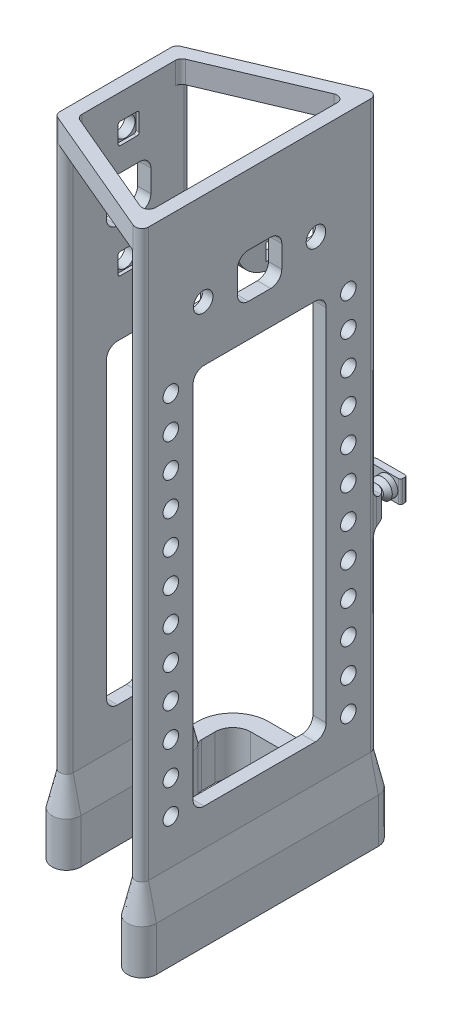
SolidWorks part; units mm, degrees
ref_plane "Front Plane" through (0, 0, 0) normal (0, 0, 1) x (1, 0, 0)
ref_plane "Top Plane" through (0, 0, 0) normal (0, 1, 0) x (1, 0, 0)
ref_plane "Right Plane" through (0, 0, 0) normal (1, 0, 0) x (0, 0, -1)
sketch "Sketch3" plane through (0, 0, 0) normal (0, 1, 0) x (1, 0, 0)
  line L0 (0, 83.3807) -> (0, -77.8886) construction
  line L1 (-38.4941, 0) -> (38.1013, 0) construction
  line L2 (-14.75, 446.5322) -> (-14.75, -531.1458) construction
  line L3 (-16.75, 12.5) -> (-16.75, -12.5)
  line L4 (-12.75, 12.5) -> (-12.75, -12.5)
  line L5 (-11.5, 12.5) -> (-11.5, -12.5)
  line L6 (-18, 12.5) -> (-18, -12.5)
  line L7 (11.5, 25) -> (11.5, -25)
  line L8 (12.75, 25) -> (12.75, -25)
  line L9 (16.75, 25) -> (16.75, -25)
  line L10 (18, 25) -> (18, -25)
  arc A0 (-16.75, 12.5) -> (-12.75, 12.5) centre (-14.75, 12.5) cw
  arc A1 (-16.75, -12.5) -> (-12.75, -12.5) centre (-14.75, -12.5) ccw
  arc A2 (-18, -12.5) -> (-11.5, -12.5) centre (-14.75, -12.5) ccw
  arc A3 (-18, 12.5) -> (-11.5, 12.5) centre (-14.75, 12.5) cw
  arc A4 (18, -25) -> (11.5, -25) centre (14.75, -25) cw
  arc A5 (16.75, -25) -> (12.75, -25) centre (14.75, -25) cw
  arc A6 (16.75, 25) -> (12.75, 25) centre (14.75, 25) ccw
  arc A7 (18, 25) -> (11.5, 25) centre (14.75, 25) ccw
  point P10 (-12.75, 0)
  point P15 (-16.75, 0)
  dimension "D3" = 1.25
  dimension "D1" = 2
  dimension "D2" = 25
  dimension "D5" = 14.75
  dimension "D4" = 50
  dimension "D6" = 1.25
extrude "LowerColumnAttachment" add sketch "Sketch3" along normal blind 7.5
sketch "Sketch4" plane through (0, 7.5, 0) normal (0, 1, 0) x (1, 0, 0)
  line L0 (-11.5, -12.5) -> (-11.5, 12.5) construction
  line L1 (-18, 12.5) -> (-18, -12.5) construction
  line L2 (18, -25) -> (18, 25) construction
  line L3 (11.5, 25) -> (11.5, -25) construction
  line L4 (-11.5, -12.5) -> (-11.5, 12.5)
  line L5 (-18, 12.5) -> (-18, -12.5)
  line L6 (18, -25) -> (18, 25)
  line L7 (11.5, 25) -> (11.5, -25)
  arc A0 (-18, -12.5) -> (-11.5, -12.5) centre (-14.75, -12.5) ccw construction
  arc A1 (-11.5, 12.5) -> (-18, 12.5) centre (-14.75, 12.5) ccw construction
  arc A2 (18, 25) -> (11.5, 25) centre (14.75, 25) ccw construction
  arc A3 (11.5, -25) -> (18, -25) centre (14.75, -25) ccw construction
  arc A4 (-18, -12.5) -> (-11.5, -12.5) centre (-14.75, -12.5) ccw
  arc A5 (-11.5, 12.5) -> (-18, 12.5) centre (-14.75, 12.5) ccw
  arc A6 (18, 25) -> (11.5, 25) centre (14.75, 25) ccw
  arc A7 (11.5, -25) -> (18, -25) centre (14.75, -25) ccw
extrude "LowerColumnAttachmentCover" add sketch "Sketch4" along normal blind 2.5
sketch "Sketch5" plane through (0, 10, 0) normal (0, 1, 0) x (1, 0, 0)
  line L2 (-18, 12.5) -> (-18, -12.5) construction
  line L3 (-11.5, -12.5) -> (-11.5, 12.5) construction
  line L56 (-11.5, -12.5) -> (-11.5, 12.5) construction
  line L57 (-18, 12.5) -> (-18, -12.5) construction
  line L58 (-16.25, 12.5) -> (-16.25, -12.5)
  line L59 (-13.25, -12.5) -> (-13.25, 12.5)
  line L60 (18, -25) -> (18, 25) construction
  line L61 (11.5, 25) -> (11.5, -25) construction
  line L62 (18, -25) -> (18, 25) construction
  line L63 (11.5, 25) -> (11.5, -25) construction
  line L64 (16.25, -25) -> (16.25, 25)
  line L65 (13.25, 25) -> (13.25, -25)
  arc A2 (-18, -12.5) -> (-11.5, -12.5) centre (-14.75, -12.5) ccw construction
  arc A3 (-11.5, 12.5) -> (-18, 12.5) centre (-14.75, 12.5) ccw construction
  arc A56 (-11.5, 12.5) -> (-18, 12.5) centre (-14.75, 12.5) ccw construction
  arc A57 (-18, -12.5) -> (-11.5, -12.5) centre (-14.75, -12.5) ccw construction
  arc A58 (-13.25, 12.5) -> (-16.25, 12.5) centre (-14.75, 12.5) ccw
  arc A59 (-16.25, -12.5) -> (-13.25, -12.5) centre (-14.75, -12.5) ccw
  arc A60 (18, 25) -> (11.5, 25) centre (14.75, 25) ccw construction
  arc A61 (11.5, -25) -> (18, -25) centre (14.75, -25) ccw construction
  arc A62 (18, 25) -> (11.5, 25) centre (14.75, 25) ccw construction
  arc A63 (11.5, -25) -> (18, -25) centre (14.75, -25) ccw construction
  arc A64 (16.25, 25) -> (13.25, 25) centre (14.75, 25) ccw
  arc A65 (13.25, -25) -> (16.25, -25) centre (14.75, -25) ccw
  dimension "D1" = 1.75
  dimension "D2" = 1.75
extrude "UpperColumnExtrude" add sketch "Sketch5" along normal blind 130
sketch "Sketch6" plane through (16.25, 0, 0) normal (1, 0, 0) x (0, 0, -1)
  line L0 (0, 199.0142) -> (0, -58.1482) construction
  line L1 (20, 27.5) -> (20, 35) construction
  line L2 (-15, 28.25) -> (-15, 109.25)
  line L3 (-12.5, 111.75) -> (12.5, 111.75)
  line L4 (15, 28.25) -> (15, 109.25)
  line L5 (-12.5, 25.75) -> (12.5, 25.75)
  line L7 (-466.9223, 0) -> (90.0452, 0) construction
  line L8 (-25, 140) -> (-25, 10) construction
  line L9 (-25, 10) -> (25, 10) construction
  arc A0 (-15, 109.25) -> (-12.5, 111.75) centre (-12.5, 109.25) cw
  arc A1 (15, 109.25) -> (12.5, 111.75) centre (12.5, 109.25) ccw
  arc A2 (-15, 28.25) -> (-12.5, 25.75) centre (-12.5, 28.25) ccw
  arc A3 (15, 28.25) -> (12.5, 25.75) centre (12.5, 28.25) cw
  circle A4 centre (-20, 27.5) radius 1.75
  circle A5 centre (20, 27.5) radius 1.75
  circle A6 centre (20, 35) radius 1.75
  circle A7 centre (-20, 35) radius 1.75
  circle A8 centre (20, 42.5) radius 1.75
  circle A9 centre (-20, 42.5) radius 1.75
  circle A10 centre (20, 50) radius 1.75
  circle A11 centre (-20, 50) radius 1.75
  circle A12 centre (20, 57.5) radius 1.75
  circle A13 centre (-20, 57.5) radius 1.75
  circle A14 centre (20, 65) radius 1.75
  circle A15 centre (-20, 65) radius 1.75
  circle A16 centre (20, 72.5) radius 1.75
  circle A17 centre (-20, 72.5) radius 1.75
  circle A18 centre (20, 80) radius 1.75
  circle A19 centre (-20, 80) radius 1.75
  circle A20 centre (20, 87.5) radius 1.75
  circle A21 centre (-20, 87.5) radius 1.75
  circle A22 centre (20, 95) radius 1.75
  circle A23 centre (-20, 95) radius 1.75
  circle A24 centre (20, 102.5) radius 1.75
  circle A25 centre (-20, 102.5) radius 1.75
  circle A26 centre (20, 110) radius 1.75
  circle A27 centre (-20, 110) radius 1.75
  dimension "D3" = 2.5
  dimension "D7" = 3.5
  dimension "D2" = 2.5
  dimension "D4" = 2.5
  dimension "D10" = 2.5
  dimension "D1" = 30
  dimension "D5" = 5
  dimension "D6" = 17.5
  dimension "D9" = 7.5
  dimension "D8" = 12
extrude "HolesCut" cut sketch "Sketch6" against normal up to next (3 mm away)
sketch "Sketch7" plane through (0, 140, 0) normal (0, 1, 0) x (1, 0, 0)
  line L0 (14.1648, 26.3811) -> (-15.3352, 13.8811)
  line L1 (16.25, -25) -> (16.25, 25) construction
  line L2 (-16.25, 12.5) -> (-16.25, -12.5) construction
  line L3 (16.25, -25) -> (16.25, 25)
  line L4 (-16.25, 12.5) -> (-16.25, -12.5)
  line L5 (14.1648, -26.3811) -> (-15.3352, -13.8811)
  arc A0 (16.25, -25) -> (14.1648, -26.3811) centre (14.75, -25) cw
  arc A1 (-16.25, -12.5) -> (-15.3352, -13.8811) centre (-14.75, -12.5) ccw
  arc A2 (16.25, 25) -> (14.1648, 26.3811) centre (14.75, 25) ccw
  arc A3 (-16.25, 12.5) -> (-15.3352, 13.8811) centre (-14.75, 12.5) cw
  arc A4 (13.25, -25) -> (16.25, -25) centre (14.75, -25) ccw construction
  arc A5 (-16.25, -12.5) -> (-13.25, -12.5) centre (-14.75, -12.5) ccw construction
  arc A6 (-13.25, 12.5) -> (-16.25, 12.5) centre (-14.75, 12.5) ccw construction
  arc A7 (16.25, 25) -> (13.25, 25) centre (14.75, 25) ccw construction
extrude "TopSectionExtrude" add sketch "Sketch7" along normal blind 5
sketch "Sketch11" plane through (0, 145, 0) normal (0, 1, 0) x (1, 0, 0)
  line L4 (-13.25, -10.513) -> (-13.25, 10.513)
  line L5 (-12.3352, 11.8941) -> (11.1648, 21.8517)
  line L6 (-15.3352, -13.8811) -> (14.1648, -26.3811) construction
  line L7 (14.1648, 26.3811) -> (-15.3352, 13.8811) construction
  line L8 (13.25, -20.4706) -> (13.25, 20.4706)
  line L9 (-12.3352, -11.8941) -> (11.1648, -21.8517)
  line L10 (16.25, -25) -> (16.25, 25) construction
  line L11 (-16.25, 12.5) -> (-16.25, -12.5) construction
  arc A1 (-13.25, 10.513) -> (-12.3352, 11.8941) centre (-11.75, 10.513) cw
  arc A2 (13.25, 20.4706) -> (11.1648, 21.8517) centre (11.75, 20.4706) ccw
  arc A3 (-13.25, -10.513) -> (-12.3352, -11.8941) centre (-11.75, -10.513) ccw
  arc A4 (13.25, -20.4706) -> (11.1648, -21.8517) centre (11.75, -20.4706) cw
  dimension "D1" = 3
  dimension "D5" = 1.5
  dimension "D6" = 1.5
  dimension "D7" = 1.5
  dimension "D8" = 1.5
  dimension "D2" = 3
  dimension "D3" = 3
  dimension "D4" = 3
extrude "TopSectionCut" cut sketch "Sketch11" against normal up to next
chamfer "CounterWeightPassChamfer" distance 1.75 distance2 7.5 8 edges at (-16.25, 10, 0) (-14.75, 10, 14) (-14.75, 10, -14) (-13.25, 10, 0) (16.25, 10, 0) (14.75, 10, -26.5) (14.75, 10, 26.5) (13.25, 10, 0)
sketch "Sketch8" plane through (16.25, 0, 0) normal (1, 0, 0) x (0, 0, -1)
  line L1 (13.4332, 124.25) -> (-60.6379, 124.25) construction
  line L2 (0, 154.8726) -> (0, -73.7622) construction
  line L3 (-25, 145) -> (25, 145) construction
  circle A0 centre (12.7, 124.25) radius 2.2
  circle A1 centre (-12.7, 124.25) radius 2.2
  dimension "D1" = 4.4
  dimension "D2" = 12.7
  dimension "D5" = 4.4
  dimension "D3" = 12.7
  dimension "D4" = 20.75
extrude "SupportBearingWideHoles" cut sketch "Sketch8" against normal up to next
sketch "Sketch9" plane through (13.25, 0, 0) normal (-1, 0, 0) x (0, 0, 1)
  line L0 (0, 153.5325) -> (0, -8.1993) construction
  line L1 (12.7, 126.45) -> (12.7, 122.05) construction
  line L2 (14.9, 124.25) -> (10.5, 124.25) construction
  line L3 (10.325, 126.125) -> (10.325, 122.375)
  line L4 (10.825, 126.625) -> (14.575, 126.625)
  line L5 (10.825, 121.875) -> (14.575, 121.875)
  line L6 (15.075, 126.125) -> (15.075, 122.375)
  line L7 (-15.075, 126.125) -> (-15.075, 122.375)
  line L8 (-10.825, 121.875) -> (-14.575, 121.875)
  line L9 (-10.325, 126.125) -> (-10.325, 122.375)
  line L10 (-10.825, 126.625) -> (-14.575, 126.625)
  arc A2 (10.325, 126.125) -> (10.825, 126.625) centre (10.825, 126.125) cw
  arc A3 (10.325, 122.375) -> (10.825, 121.875) centre (10.825, 122.375) ccw
  arc A4 (15.075, 122.375) -> (14.575, 121.875) centre (14.575, 122.375) cw
  arc A5 (15.075, 126.125) -> (14.575, 126.625) centre (14.575, 126.125) ccw
  circle A7 centre (12.7, 124.25) radius 2.2 construction
  arc A8 (-15.075, 126.125) -> (-14.575, 126.625) centre (-14.575, 126.125) cw
  arc A9 (-15.075, 122.375) -> (-14.575, 121.875) centre (-14.575, 122.375) ccw
  arc A10 (-10.325, 122.375) -> (-10.825, 121.875) centre (-10.825, 122.375) cw
  arc A11 (-10.325, 126.125) -> (-10.825, 126.625) centre (-10.825, 126.125) ccw
  dimension "D3" = 0.5
  dimension "D1" = 4.75
  dimension "D2" = 4.75
extrude "SupportBearingWideCutOut" cut sketch "Sketch9" against normal blind 0.75
sketch "Sketch12" plane through (-13.25, 0, 0) normal (1, 0, 0) x (0, 0, -1)
  line L0 (0, 142.2043) -> (0, -19.6949) construction
  line L1 (-30.5042, 124.25) -> (31.5208, 124.25) construction
  line L2 (-25, 145) -> (25, 145) construction
  circle A0 centre (0, 136.95) radius 2.2
  circle A1 centre (0, 111.55) radius 2.2
  dimension "D1" = 4.4
  dimension "D2" = 4.4
  dimension "D3" = 20.75
  dimension "D4" = 12.7
  dimension "D5" = 12.7
extrude "SupportBearingNarrowHoles" cut sketch "Sketch12" against normal up to next
sketch "Sketch13" plane through (-13.25, 0, 0) normal (1, 0, 0) x (0, 0, -1)
  line L0 (2.2, 136.95) -> (-2.2, 136.95) construction
  line L1 (0, 139.15) -> (0, 134.75) construction
  line L2 (2.375, 135.075) -> (2.375, 138.825)
  line L3 (-1.875, 139.325) -> (1.875, 139.325)
  line L4 (-2.375, 135.075) -> (-2.375, 138.825)
  line L5 (-1.875, 134.575) -> (1.875, 134.575)
  line L6 (-12.7, 124.25) -> (12.7, 124.25) construction
  line L7 (-2.375, 113.425) -> (-2.375, 109.675)
  line L8 (-1.875, 109.175) -> (1.875, 109.175)
  line L9 (2.375, 113.425) -> (2.375, 109.675)
  line L10 (-1.875, 113.925) -> (1.875, 113.925)
  circle A0 centre (0, 136.95) radius 2.2 construction
  arc A1 (2.375, 138.825) -> (1.875, 139.325) centre (1.875, 138.825) ccw
  arc A2 (-2.375, 138.825) -> (-1.875, 139.325) centre (-1.875, 138.825) cw
  arc A3 (2.375, 135.075) -> (1.875, 134.575) centre (1.875, 135.075) cw
  arc A4 (-2.375, 135.075) -> (-1.875, 134.575) centre (-1.875, 135.075) ccw
  arc A5 (-2.375, 113.425) -> (-1.875, 113.925) centre (-1.875, 113.425) cw
  arc A6 (-2.375, 109.675) -> (-1.875, 109.175) centre (-1.875, 109.675) ccw
  arc A7 (2.375, 109.675) -> (1.875, 109.175) centre (1.875, 109.675) cw
  arc A8 (2.375, 113.425) -> (1.875, 113.925) centre (1.875, 113.425) ccw
  point P7 (-2.375, 136.95)
  point P16 (0, 139.325)
  point P22 (2.375, 136.95)
  dimension "D1" = 0.5
  dimension "D2" = 4.75
  dimension "D3" = 4.75
extrude "SupportBearingNarrowCutOut" cut sketch "Sketch13" against normal blind 0.75
sketch "Sketch14" plane through (-16.25, 0, 0) normal (-1, 0, 0) x (0, 0, 1)
  line L0 (0, 149.8595) -> (0, -14.9405) construction
  line L1 (-5, 94.25) -> (-5, 28.25)
  line L2 (-2.5, 96.75) -> (2.5, 96.75)
  line L3 (-2.5, 25.75) -> (2.5, 25.75)
  line L4 (5, 94.25) -> (5, 28.25)
  line L5 (-8.5712, 124.25) -> (7.7144, 124.25) construction
  line L6 (-5, 121.75) -> (-5, 126.75)
  line L7 (-2.5, 129.25) -> (2.5, 129.25)
  line L8 (5, 121.75) -> (5, 126.75)
  line L9 (-2.5, 119.25) -> (2.5, 119.25)
  arc A0 (-5, 94.25) -> (-2.5, 96.75) centre (-2.5, 94.25) cw
  arc A1 (-5, 28.25) -> (-2.5, 25.75) centre (-2.5, 28.25) ccw
  arc A2 (5, 28.25) -> (2.5, 25.75) centre (2.5, 28.25) cw
  arc A3 (5, 94.25) -> (2.5, 96.75) centre (2.5, 94.25) ccw
  circle A4 centre (20, 27.5) radius 1.75 construction
  circle A6 centre (0, 111.55) radius 2.2 construction
  circle A7 centre (0, 136.95) radius 2.2 construction
  arc A8 (-5, 126.75) -> (-2.5, 129.25) centre (-2.5, 126.75) cw
  arc A9 (5, 126.75) -> (2.5, 129.25) centre (2.5, 126.75) ccw
  arc A10 (-5, 121.75) -> (-2.5, 119.25) centre (-2.5, 121.75) ccw
  arc A11 (5, 121.75) -> (2.5, 119.25) centre (2.5, 121.75) cw
  circle A14 centre (20, 95) radius 1.75 construction
  dimension "D2" = 2.5
  dimension "D3" = 2.5
  dimension "D1" = 10
  dimension "D4" = 10
  dimension "D5" = 10
extrude "SupportBearingNarrowCentreCutOut" cut sketch "Sketch14" against normal up to next
sketch "Sketch15" plane through (16.25, 0, 0) normal (1, 0, 0) x (0, 0, -1)
  line L0 (2.5, 129.25) -> (-2.5, 129.25) construction
  line L1 (5, 121.75) -> (5, 126.75) construction
  line L2 (-2.5, 119.25) -> (2.5, 119.25) construction
  line L3 (-5, 126.75) -> (-5, 121.75) construction
  line L4 (2.5, 129.25) -> (-2.5, 129.25)
  line L5 (5, 121.75) -> (5, 126.75)
  line L6 (-2.5, 119.25) -> (2.5, 119.25)
  line L7 (-5, 126.75) -> (-5, 121.75)
  arc A0 (5, 126.75) -> (2.5, 129.25) centre (2.5, 126.75) ccw construction
  arc A1 (2.5, 119.25) -> (5, 121.75) centre (2.5, 121.75) ccw construction
  arc A2 (-5, 121.75) -> (-2.5, 119.25) centre (-2.5, 121.75) ccw construction
  arc A3 (-2.5, 129.25) -> (-5, 126.75) centre (-2.5, 126.75) ccw construction
  arc A4 (5, 126.75) -> (2.5, 129.25) centre (2.5, 126.75) ccw
  arc A5 (2.5, 119.25) -> (5, 121.75) centre (2.5, 121.75) ccw
  arc A6 (-5, 121.75) -> (-2.5, 119.25) centre (-2.5, 121.75) ccw
  arc A7 (-2.5, 129.25) -> (-5, 126.75) centre (-2.5, 126.75) ccw
extrude "SupportBearingWideCentreCutOut" cut sketch "Sketch15" against normal up to next
ref_plane "LimitSwitchSupportPlane" through (0, 105, 0) normal (0, 1, 0) x (1, 0, 0)
sketch "Sketch16" plane through (0, 105, 0) normal (0, 1, 0) x (1, 0, 0)
  line L0 (-15.5, 15) -> (-15.5, 12.5)
  line L1 (-15.5, 12.5) -> (-14, 12.5)
  line L2 (-14, 12.5) -> (-14, 15)
  line L3 (-13.7, 15.7141) -> (-11.25, 18.1156)
  line L4 (-14.75, -19.9286) -> (-14.75, 49.3932) construction
  line L5 (-11.5, -12.5) -> (-11.5, 12.5) construction
  line L6 (-18, 12.5) -> (-18, -12.5) construction
  line L7 (-16.25, 12.5) -> (-18, 12.5) construction
  line L8 (-10.5, 19.901) -> (-10.5, 30)
  line L9 (-10.5, 30) -> (-12, 30)
  line L10 (-12, 30) -> (-12, 19.901)
  line L11 (-14.75, 16.7854) -> (-12.3, 19.1868)
  line L12 (-11.25, 31.213) -> (-11.25, 17.258) construction
  arc A0 (-15.5, 15) -> (-14.75, 16.7854) centre (-13, 15) cw
  arc A1 (-14, 15) -> (-13.7, 15.7141) centre (-13, 15) cw
  arc A2 (-12, 19.901) -> (-12.3, 19.1868) centre (-13, 19.901) cw
  arc A3 (-10.5, 19.901) -> (-11.25, 18.1156) centre (-13, 19.901) cw
  dimension "D1" = 2.5
  dimension "D2" = 1.5
  dimension "D3" = 1.5
  dimension "D4" = 17.5
  dimension "D5" = 3.5
extrude "LimitSwitchSupport" add sketch "Sketch16" along normal blind 2.75 and the other way blind 2.75
sketch "Sketch17" plane through (-12, 0, 0) normal (-1, 0, 0) x (0, 0, 1)
  line L0 (-30, 102.25) -> (-30, 107.75) construction
  circle A0 centre (-30, 105) radius 8.75
  dimension "D1" = 17.5
extrude "LimitSwitchBase" add sketch "Sketch17" against normal up to surface (1.5 mm away) up to face at (-10.5, 105, -24.9505)
sketch "Sketch18" plane through (-10.5, 0, 0) normal (1, 0, 0) x (0, 0, -1)
  line L0 (52.3748, 105) -> (24.007, 105) construction
  line L1 (32.45, 99) -> (28.15, 99)
  line L2 (32.45, 99) -> (32.45, 102)
  line L3 (32.45, 102) -> (28.15, 102)
  line L4 (28.15, 99) -> (28.15, 102)
  line L5 (30, 94.3801) -> (30, 115.9875) construction
  line L6 (38.75, 86.7525) -> (38.75, 110.4116) construction
  line L7 (21.25, 94.7814) -> (21.25, 120.2253) construction
  line L8 (32.45, 111) -> (28.15, 111)
  line L9 (19.901, 102.25) -> (21.6934, 102.25) construction
  line L10 (19.901, 107.75) -> (21.6934, 107.75) construction
  line L11 (28.15, 111) -> (28.15, 108)
  line L12 (32.45, 108) -> (28.15, 108)
  line L13 (32.45, 111) -> (32.45, 108)
  circle A0 centre (36.1, 105) radius 1.75
  circle A1 centre (23.9, 105) radius 1.75
  arc A2 (21.6934, 102.25) -> (21.6934, 107.75) centre (30, 105) ccw construction
  dimension "D2" = 3.5
  dimension "D3" = 3.5
  dimension "D1" = 3
  dimension "D4" = 12.2
  dimension "D5" = 3
  dimension "D6" = 4.3
  dimension "D7" = 1.85
extrude "LimitSwitchBaseHoles" cut sketch "Sketch18" against normal up to next
chamfer "LimitSwitchInsertionChamfer" distance 0.75 distance2 1.5 2 edges at (-10.5, 99, -30.3) (-10.5, 111, -30.3)
fillet "LimitSwitchSupportFillet" radius 1 6 edges at (-14, 105, -13.799) (-15.5, 105, -13.799) (-11.25, 102.25, -21.6934) (-11.25, 107.75, -21.6934) (-14.75, 102.25, -14) (-14.75, 107.75, -14)
ref_plane "PCBConnectorPlane" through (0, 63.05, 0) normal (0, 1, 0) x (1, 0, 0)
sketch "Sketch19" plane through (0, 63.05, 0) normal (0, 1, 0) x (1, 0, 0)
  line L0 (13.25, 25) -> (16.25, 25) construction
  line L1 (14.75, -26.1065) -> (14.75, 38.8663) construction
  line L3 (15.5, 25) -> (15.5, 27)
  line L4 (14, 25) -> (15.5, 25)
  line L5 (12.5, 30) -> (8, 30)
  line L6 (7.5, 30.5) -> (7.5, 33)
  line L7 (8, 33.5) -> (14, 33.5)
  line L8 (14.5, 34) -> (14.5, 34.5)
  line L9 (14, 35) -> (8, 35)
  line L10 (6, 33) -> (6, 30.5)
  line L11 (8, 28.5) -> (12.5, 28.5)
  line L12 (14, 27) -> (14, 25)
  line L13 (13.25, -20.4706) -> (13.25, 20.4706) construction
  line L14 (16.25, -25) -> (16.25, 25) construction
  arc A0 (14, 27) -> (12.5, 28.5) centre (12.5, 27) ccw
  arc A1 (15.5, 27) -> (12.5, 30) centre (12.5, 27) ccw
  arc A2 (8, 30) -> (7.5, 30.5) centre (8, 30.5) cw
  arc A3 (8, 28.5) -> (6, 30.5) centre (8, 30.5) cw
  arc A4 (6, 33) -> (8, 35) centre (8, 33) cw
  arc A5 (7.5, 33) -> (8, 33.5) centre (8, 33) cw
  arc A6 (14, 35) -> (14.5, 34.5) centre (14, 34.5) cw
  arc A7 (14.5, 34) -> (14, 33.5) centre (14, 34) cw
  dimension "D4" = 3.5
  dimension "D5" = 0.25
  dimension "D6" = 1.5
  dimension "D7" = 0.5
  dimension "D8" = 0.5
  dimension "D1" = 1.5
  dimension "D2" = 5
  dimension "D3" = 7.25
extrude "PCBConnectorClip" add sketch "Sketch19" along normal blind 2.5 and the other way blind 2.5
sketch "Sketch20" plane through (0, 0, -33.5) normal (0, 0, 1) x (1, 0, 0)
  line L0 (19.8, 63.05) -> (-19.8, 63.05) construction
  line L1 (7.5, 60.55) -> (7.5, 65.55) construction
  circle A0 centre (11.65, 63.05) radius 2.25
  dimension "D1" = 4.5
  dimension "D2" = 4.15
extrude "PCBConnectorNotch" add sketch "Sketch20" along normal blind 2.25
chamfer "PCBConnectorNotchChamfer" distance 1 angle 45 1 edges at (13.9, 63.05, -31.25)
fillet "PCBConnectorFillet" radius 2 4 edges at (14, 63.05, -26.299) (14.75, 60.55, -26.5) (15.5, 63.05, -26.299) (14.75, 65.55, -26.5)
sketch "Sketch22" plane through (0, 0, 0) normal (0, -1, 0) x (-1, 0, 0)
  line L0 (-12.1883, 27) -> (8.75, 27)
  line L1 (12.75, 19) -> (12.75, 15.0617)
  line L2 (8.75, 23) -> (-11.5, 23)
  line L4 (-12.1883, 27) -> (-14.75, 27) construction
  line L5 (16.75, 19) -> (16.75, 15.0617)
  line L8 (12.75, -12.5) -> (12.75, 12.5) construction
  line L9 (16.75, 12.5) -> (16.75, -12.5) construction
  line L10 (12.75, -12.5) -> (12.75, 12.5) construction
  line L11 (16.75, 12.5) -> (16.75, -12.5) construction
  line L12 (-11.5, 23) -> (-11.5, 25)
  arc A0 (-11.5, 25) -> (-18, 25) centre (-14.75, 25) ccw construction
  arc A1 (8.75, 27) -> (16.75, 19) centre (8.75, 19) cw
  arc A2 (12.75, 19) -> (8.75, 23) centre (8.75, 19) ccw
  arc A3 (12.75, 15.0617) -> (16.75, 15.0617) centre (14.75, 12.5) cw
  arc A4 (18, 12.5) -> (11.5, 12.5) centre (14.75, 12.5) ccw construction
  arc A5 (-12.75, 25) -> (-16.75, 25) centre (-14.75, 25) ccw construction
  arc A6 (-12.1883, 27) -> (-11.5, 25) centre (-14.75, 25) cw
  dimension "D1" = 4
extrude "LowerColumnStructuralSupport" add sketch "Sketch22" against normal blind 10
fillet "LowerColumnStructuralSupportFillet" radius 2 4 edges at (-16.75, 5, -15.0617) (-12.75, 5, -15.0617) (11.5, 5, -23) (12.1883, 5, -27)
